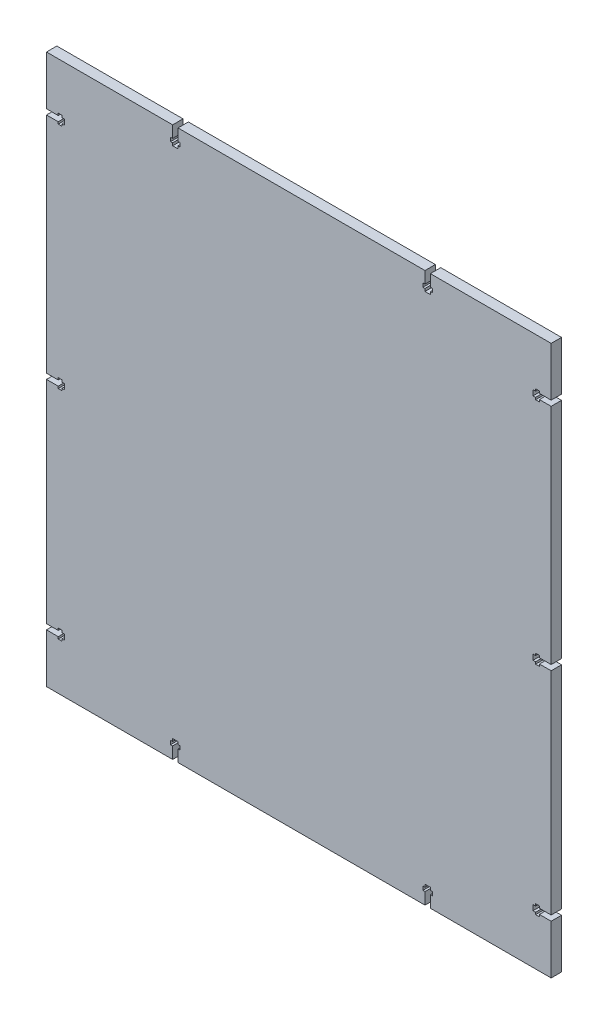
SolidWorks part; units mm, degrees
material "Клен"
ref_plane "Спереди" through (0, 0, 0) normal (0, 0, 1) x (1, 0, 0)
ref_plane "Сверху" through (0, 0, 0) normal (0, 1, 0) x (1, 0, 0)
ref_plane "Справа" through (0, 0, 0) normal (1, 0, 0) x (0, 0, -1)
sketch "Эскиз1" plane through (0, 0, 0) normal (0, 0, 1) x (1, 0, 0)
  line L1 (0, 0) -> (73, 0)
  line L2 (0, 0) -> (0, -28.45)
  line L3 (0, -318) -> (73, -318)
  line L4 (292, 0) -> (292, -28.45)
  line L15 (146, 38.6612) -> (146, -369.0135) construction
  line L16 (338.8892, -160.95) -> (-53.634, -160.95) construction
  line L17 (-48.9358, -30) -> (338.8892, -30) construction
  line L18 (-48.9358, -289.55) -> (329.134, -289.55) construction
  line L76 (0, -289.55) -> (0, -318)
  line L80 (73, 38.6612) -> (73, -369.0135) construction
  line L81 (219, 38.6612) -> (219, -369.0135) construction
  line L82 (76.1, 0) -> (219, 0)
  line L83 (222.1, 0) -> (292, 0)
  line L84 (76.1, -318) -> (219, -318)
  line L85 (222.1, -318) -> (292, -318)
  line L86 (338.8892, -28.45) -> (-48.9358, -28.45) construction
  line L87 (285.2, -28.45) -> (285.2, -27.25)
  line L88 (283, -32.75) -> (285.2, -32.75)
  line L89 (283, -28.45) -> (281.5, -28.45)
  line L90 (285.2, -27.25) -> (283, -27.25)
  line L91 (292, -28.45) -> (285.2, -28.45)
  line L92 (281.5, -31.55) -> (283, -31.55)
  line L93 (222.1, -6.8) -> (222.1, 0)
  line L94 (222.1, -9) -> (223.3, -9)
  line L95 (219, -10.5) -> (222.1, -10.5)
  line L96 (222.1, -10.5) -> (222.1, -9)
  line L97 (219, 0) -> (219, -6.8)
  line L98 (219, -6.8) -> (217.8, -6.8)
  line L99 (223.3, -9) -> (223.3, -6.8)
  line L100 (217.8, -6.8) -> (217.8, -9)
  line L101 (223.3, -6.8) -> (222.1, -6.8)
  line L102 (217.8, -9) -> (219, -9)
  line L103 (219, -9) -> (219, -10.5)
  line L104 (76.1, -6.8) -> (76.1, 0)
  line L105 (76.1, -9) -> (77.3, -9)
  line L106 (73, -10.5) -> (76.1, -10.5)
  line L107 (76.1, -10.5) -> (76.1, -9)
  line L108 (73, 0) -> (73, -6.8)
  line L109 (73, -6.8) -> (71.8, -6.8)
  line L110 (77.3, -9) -> (77.3, -6.8)
  line L111 (71.8, -6.8) -> (71.8, -9)
  line L112 (77.3, -6.8) -> (76.1, -6.8)
  line L113 (71.8, -9) -> (73, -9)
  line L114 (73, -9) -> (73, -10.5)
  line L115 (73, -309) -> (73, -307.5)
  line L116 (71.8, -309) -> (73, -309)
  line L117 (77.3, -311.2) -> (76.1, -311.2)
  line L118 (71.8, -311.2) -> (71.8, -309)
  line L119 (77.3, -309) -> (77.3, -311.2)
  line L120 (73, -311.2) -> (71.8, -311.2)
  line L121 (73, -318) -> (73, -311.2)
  line L122 (76.1, -307.5) -> (76.1, -309)
  line L123 (73, -307.5) -> (76.1, -307.5)
  line L124 (76.1, -309) -> (77.3, -309)
  line L125 (76.1, -311.2) -> (76.1, -318)
  line L126 (219, -309) -> (219, -307.5)
  line L127 (217.8, -309) -> (219, -309)
  line L128 (223.3, -311.2) -> (222.1, -311.2)
  line L129 (217.8, -311.2) -> (217.8, -309)
  line L130 (223.3, -309) -> (223.3, -311.2)
  line L131 (219, -311.2) -> (217.8, -311.2)
  line L132 (219, -318) -> (219, -311.2)
  line L133 (222.1, -307.5) -> (222.1, -309)
  line L134 (219, -307.5) -> (222.1, -307.5)
  line L135 (222.1, -309) -> (223.3, -309)
  line L136 (222.1, -311.2) -> (222.1, -318)
  line L137 (285.2, -32.75) -> (285.2, -31.55)
  line L138 (285.2, -31.55) -> (292, -31.55)
  line L139 (281.5, -28.45) -> (281.5, -31.55)
  line L140 (283, -27.25) -> (283, -28.45)
  line L141 (283, -31.55) -> (283, -32.75)
  line L142 (292, -33.1) -> (292, -31.55)
  line L143 (285.2, -286.45) -> (285.2, -285.25)
  line L144 (285.2, -289.55) -> (292, -289.55)
  line L145 (281.5, -286.45) -> (281.5, -289.55)
  line L146 (283, -285.25) -> (283, -286.45)
  line L147 (283, -286.45) -> (281.5, -286.45)
  line L148 (281.5, -289.55) -> (283, -289.55)
  line L149 (292, -286.45) -> (285.2, -286.45)
  line L150 (285.2, -285.25) -> (283, -285.25)
  line L151 (283, -289.55) -> (283, -290.75)
  line L152 (283, -290.75) -> (285.2, -290.75)
  line L153 (285.2, -290.75) -> (285.2, -289.55)
  line L155 (292, -289.55) -> (292, -318)
  line L157 (9, -31.55) -> (9, -32.75)
  line L158 (9, -27.25) -> (9, -28.45)
  line L159 (10.5, -28.45) -> (10.5, -31.55)
  line L160 (6.8, -31.55) -> (0, -31.55)
  line L161 (6.8, -32.75) -> (6.8, -31.55)
  line L162 (10.5, -31.55) -> (9, -31.55)
  line L163 (0, -28.45) -> (6.8, -28.45)
  line L164 (6.8, -27.25) -> (9, -27.25)
  line L165 (9, -28.45) -> (10.5, -28.45)
  line L166 (9, -32.75) -> (6.8, -32.75)
  line L167 (6.8, -28.45) -> (6.8, -27.25)
  line L179 (6.8, -290.75) -> (6.8, -289.55)
  line L180 (9, -290.75) -> (6.8, -290.75)
  line L181 (9, -289.55) -> (9, -290.75)
  line L182 (6.8, -285.25) -> (9, -285.25)
  line L183 (0, -286.45) -> (6.8, -286.45)
  line L184 (10.5, -289.55) -> (9, -289.55)
  line L185 (9, -286.45) -> (10.5, -286.45)
  line L186 (9, -285.25) -> (9, -286.45)
  line L187 (10.5, -286.45) -> (10.5, -289.55)
  line L188 (6.8, -289.55) -> (0, -289.55)
  line L189 (6.8, -286.45) -> (6.8, -285.25)
  line L191 (292, -33.1) -> (292, -160.95)
  line L192 (281.5, -160.95) -> (281.5, -164.05)
  line L193 (281.5, -164.05) -> (283, -164.05)
  line L194 (283, -160.95) -> (281.5, -160.95)
  line L195 (285.2, -164.05) -> (292, -164.05)
  line L196 (283, -165.25) -> (285.2, -165.25)
  line L197 (285.2, -165.25) -> (285.2, -164.05)
  line L198 (285.2, -159.75) -> (283, -159.75)
  line L199 (283, -159.75) -> (283, -160.95)
  line L200 (292, -160.95) -> (285.2, -160.95)
  line L201 (285.2, -160.95) -> (285.2, -159.75)
  line L202 (283, -164.05) -> (283, -165.25)
  line L203 (292, -164.05) -> (292, -286.45)
  line L204 (9, -164.05) -> (9, -165.25)
  line L205 (6.8, -160.95) -> (6.8, -159.75)
  line L206 (0, -160.95) -> (6.8, -160.95)
  line L207 (9, -159.75) -> (9, -160.95)
  line L208 (6.8, -159.75) -> (9, -159.75)
  line L209 (6.8, -165.25) -> (6.8, -164.05)
  line L210 (9, -165.25) -> (6.8, -165.25)
  line L211 (6.8, -164.05) -> (0, -164.05)
  line L212 (9, -160.95) -> (10.5, -160.95)
  line L213 (10.5, -164.05) -> (9, -164.05)
  line L214 (10.5, -160.95) -> (10.5, -164.05)
  line L215 (0, -31.55) -> (0, -160.95)
  line L216 (0, -286.45) -> (0, -164.05)
  dimension "D1" = 292
  dimension "D2" = 318
  dimension "D3" = 30
  dimension "D4" = 73
  dimension "D5" = 73
  dimension "D6" = 28.45
  dimension "D7" = 28.45
  dimension "D8" = 160.95
extrude "Бобышка-Вытянуть1" add sketch "Эскиз1" along normal blind 6
